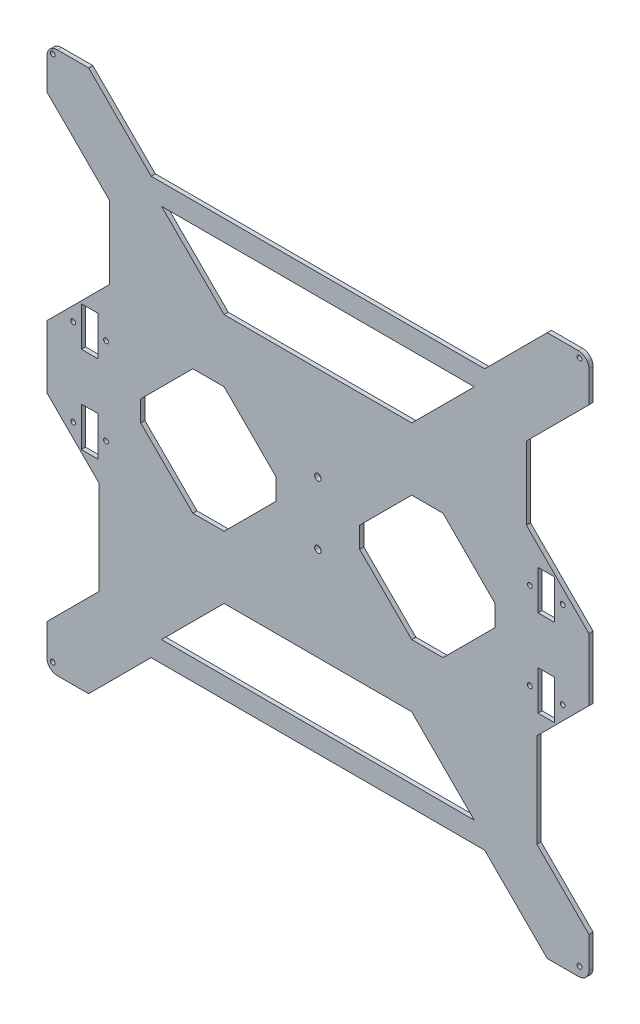
SolidWorks part; units mm, degrees
ref_plane "Front Plane" through (0, 0, 0) normal (0, 0, 1) x (1, 0, 0)
ref_plane "Top Plane" through (0, 0, 0) normal (0, 1, 0) x (1, 0, 0)
ref_plane "Right Plane" through (0, 0, 0) normal (1, 0, 0) x (0, 0, -1)
sketch "Model" plane through (0, 0, 0) normal (0, 0, 1) x (1, 0, 0)
  line L0 (38.5361, 132.6139) -> (38.5361, 132.4727)
  line L1 (38.5361, -178.6774) -> (38.5361, -178.7219)
  line L2 (-253.5639, -197.5861) -> (-253.5639, -197.7273)
  line L3 (-252.5813, 70.3317) -> (-252.5813, 25.8817)
  line L4 (-258.9313, -82.0683) -> (-258.9313, -139.2183)
  line L5 (38.5361, 132.6139) -> (38.5361, 132.4727)
  line L6 (38.5361, -178.6774) -> (38.5361, -178.7219)
  line L7 (7.7687, -139.2183) -> (7.7687, -82.0683)
  line L8 (1.4187, 25.8817) -> (1.4187, 70.3317)
  line L9 (-23.9813, 95.7317) -> (-227.1813, 95.7317)
  line L10 (-290.6813, 108.4317) -> (-252.5813, 70.3317)
  line L11 (-30.3313, -145.5683) -> (-68.4313, -107.4683)
  line L12 (-23.9813, -158.2683) -> (14.1187, -196.3683)
  line L13 (39.5187, 108.4317) -> (39.5187, 127.4817)
  line L14 (-227.1813, 95.7317) -> (-265.2813, 133.8317)
  line L15 (-220.8313, 83.0317) -> (-182.7313, 44.9317)
  line L16 (-274.6813, -57.7288) -> (-254.6813, -57.7288) construction
  line L17 (39.5187, -170.9683) -> (7.7687, -139.2183)
  line L18 (-265.2813, -196.3683) -> (-227.1813, -158.2683)
  line L19 (-182.7313, -107.4683) -> (-68.4313, -107.4683)
  line L20 (-264.6813, -57.7288) -> (-264.6813, -43.5832) construction
  line L21 (1.4187, 70.3317) -> (39.5187, 108.4317)
  line L22 (-23.9813, 95.7317) -> (14.1187, 133.8317)
  line L23 (-30.3313, 83.0317) -> (-68.4313, 44.9317)
  line L25 (-258.9313, -139.2183) -> (-290.6813, -170.9683)
  line L26 (-182.7313, 44.9317) -> (-68.4313, 44.9317)
  line L27 (-220.8313, -145.5683) -> (-182.7313, -107.4683)
  line L28 (-220.8313, -145.5683) -> (-30.3313, -145.5683)
  line L29 (-258.9313, -82.0683) -> (-290.6813, -50.3183)
  line L30 (-290.6813, -12.2183) -> (-290.6813, -50.3183)
  line L31 (-274.6813, -56.2683) -> (-274.6813, -31.2683) construction
  line L32 (-290.6813, -12.2183) -> (-252.5813, 25.8817)
  line L33 (-201.7813, -69.3683) -> (-233.5313, -37.6183)
  line L34 (-182.7313, -69.3683) -> (-201.7813, -69.3683)
  line L35 (1.4187, 25.8817) -> (39.5187, -12.2183)
  line L36 (39.5187, -12.2183) -> (39.5187, -50.3183)
  line L37 (-150.9813, -37.6183) -> (-182.7313, -69.3683)
  line L38 (39.5187, -50.3183) -> (22.4579, -67.3791)
  line L39 (22.4579, -67.3791) -> (7.7687, -82.0683)
  line L40 (-100.1813, -37.6183) -> (-100.1813, -24.9183)
  line L41 (-150.9813, -37.6183) -> (-150.9813, -24.9183)
  line L42 (-150.9813, -24.9183) -> (-182.7313, 6.8317)
  line L43 (-182.7313, 6.8317) -> (-201.7813, 6.8317)
  line L44 (-201.7813, 6.8317) -> (-233.5313, -24.9183)
  line L45 (-233.5313, -24.9183) -> (-233.5313, -37.6183)
  line L46 (-17.6313, -24.9183) -> (-17.6313, -37.6183)
  line L47 (-49.3813, 6.8317) -> (-17.6313, -24.9183)
  line L48 (-220.8313, 83.0317) -> (-30.3313, 83.0317)
  line L49 (-68.4313, 6.8317) -> (-49.3813, 6.8317)
  line L50 (-100.1813, -24.9183) -> (-68.4313, 6.8317)
  line L51 (-100.1813, -37.6183) -> (-68.4313, -69.3683)
  line L52 (-68.4313, -69.3683) -> (-49.3813, -69.3683)
  line L53 (-49.3813, -69.3683) -> (-17.6313, -37.6183)
  line L58 (-265.2813, -196.3683) -> (-284.3313, -196.3683)
  line L59 (-290.6813, -190.0183) -> (-290.6813, -170.9683)
  line L60 (-290.6813, 108.4317) -> (-290.6813, 127.4817)
  line L61 (-284.3313, 133.8317) -> (-265.2813, 133.8317)
  line L62 (14.1187, 133.8317) -> (33.1687, 133.8317)
  line L64 (39.5187, -170.9683) -> (39.5187, -190.0183)
  line L65 (33.1687, -196.3683) -> (14.1187, -196.3683)
  line L71 (-227.1813, -158.2683) -> (-23.9813, -158.2683)
  line L72 (38.5361, -178.6774) -> (38.5361, -178.7219)
  line L74 (-227.1813, -158.2683) -> (-23.9813, -158.2683)
  line L75 (38.5361, -178.6774) -> (38.5361, -178.7219)
  line L77 (-125.5813, 95.7317) -> (-125.5813, -158.2683) construction
  line L78 (-290.6813, -31.2683) -> (39.5187, -31.2683) construction
  arc A0 (33.1687, -196.3683) -> (39.5187, -190.0183) centre (33.1687, -190.0183) ccw
  arc A1 (-290.6813, -190.0183) -> (-284.3313, -196.3683) centre (-284.3313, -190.0183) ccw
  arc A2 (-290.6813, 127.4817) -> (-284.3313, 133.8317) centre (-284.3313, 127.4817) cw
  arc A3 (33.1687, 133.8317) -> (39.5187, 127.4817) centre (33.1687, 127.4817) cw
  circle A4 centre (-287.1253, -190.6025) radius 1.4605
  circle A5 centre (33.7529, -190.6025) radius 1.4605
  circle A6 centre (33.7529, 130.2757) radius 1.4605
  circle A7 centre (-287.1253, 130.2757) radius 1.4605
  circle A8 centre (-274.6813, -57.7288) radius 1.4605
  circle A9 centre (-254.6813, -57.7288) radius 1.4605
  circle A10 centre (23.5187, -57.7288) radius 1.4605
  circle A11 centre (3.5187, -57.7288) radius 1.4605
  circle A12 centre (23.5187, -4.8078) radius 1.4605
  circle A13 centre (3.5187, -4.8078) radius 1.4605
  circle A14 centre (-254.6813, -4.8078) radius 1.4605
  circle A15 centre (-274.6813, -4.8078) radius 1.4605
  circle A16 centre (-125.5813, -12.2183) radius 2
  circle A17 centre (-125.5813, -50.3183) radius 2
  point P72 (-125.5813, -31.2683)
  point P79 (-290.6813, -31.2683)
  point P114 (-125.5813, 83.0317)
  point P116 (39.5187, -31.2683)
  point P120 (-233.5313, -31.2683)
  point P129 (-150.9813, -31.2683)
  point P141 (-290.6813, -180.4933)
  point P149 (-125.5813, 44.9317)
  point P156 (-17.6313, -31.2683)
  dimension "D28" = 6.35
  dimension "D29" = 6.35
  dimension "D30" = 6.35
  dimension "D31" = 6.35
  dimension "D35" = 2.921
  dimension "D36" = 2.921
  dimension "D37" = 2.921
  dimension "D38" = 2.921
  dimension "D53" = 2.921
  dimension "D54" = 2.921
  dimension "D56" = 4
  dimension "D57" = 4
  dimension "D1" = 330.2
  dimension "D2" = 330.2
  dimension "D3" = 135
  dimension "D4" = 135
  dimension "D5" = 38.1
  dimension "D6" = 135
  dimension "D7" = 135
  dimension "D8" = 19.05
  dimension "D9" = 135
  dimension "D10" = 19.05
  dimension "D11" = 31.75
  dimension "D12" = 190.5
  dimension "D13" = 114.3
  dimension "D14" = 38.1
  dimension "D15" = 114.3
  dimension "D16" = 135
  dimension "D17" = 6.35
  dimension "D18" = 38.1
  dimension "D19" = 135
  dimension "D20" = 135
  dimension "D21" = 6.35
  dimension "D22" = 19.05
  dimension "D23" = 25.4
  dimension "D24" = 38.1
  dimension "D25" = 135
  dimension "D26" = 135
  dimension "D27" = 127
  dimension "D32" = 19.05
  dimension "D33" = 19.05
  dimension "D34" = 19.05
  dimension "D39" = 38.1
  dimension "D40" = 19.05
  dimension "D41" = 38.1
  dimension "D42" = 38.1
  dimension "D43" = 135
  dimension "D44" = 19.05
  dimension "D45" = 31.75
  dimension "D46" = 135
  dimension "D47" = 320.8782
  dimension "D48" = 320.8782
  dimension "D49" = 3.556
  dimension "D50" = 3.556
  dimension "D51" = 20
  dimension "D52" = 26
  dimension "D55" = 25
  dimension "D58" = 38.1
  dimension "D59" = 19.05
extrude "Boss-Extrude1" add sketch "Model" along normal mid plane 2.54 contours A3 L62 L22 L9 L14 L61 A2 L60 L10 L3 L32 L30 L29 L4 L25 L59 A1 L58 L18 L71 L12 L65 A0 L64 L17 L7 L39 L38 L36 L35 L8 L21 L13 A17 A16 A14 A13 A12 A10 A9 region at (-125.5808, -32.1456, 0)
sketch "Sketch1" plane through (0, 0, 1.27) normal (0, 0, 1) x (1, 0, 0)
  line L1 (-269.6813, -45.7288) -> (-259.6813, -45.7288)
  line L2 (-269.6813, -45.7288) -> (-269.6813, -69.7288)
  line L3 (-269.6813, -69.7288) -> (-259.6813, -69.7288)
  line L4 (-259.6813, -45.7288) -> (-259.6813, -69.7288)
  line L5 (-269.6813, 7.1922) -> (-259.6813, 7.1922)
  line L6 (-269.6813, 7.1922) -> (-269.6813, -16.8078)
  line L7 (-269.6813, -16.8078) -> (-259.6813, -16.8078)
  line L8 (-259.6813, 7.1922) -> (-259.6813, -16.8078)
  line L9 (8.5187, 7.1922) -> (18.5187, 7.1922)
  line L10 (8.5187, 7.1922) -> (8.5187, -16.8078)
  line L11 (8.5187, -16.8078) -> (18.5187, -16.8078)
  line L12 (18.5187, 7.1922) -> (18.5187, -16.8078)
  line L13 (8.5187, -45.7288) -> (18.5187, -45.7288)
  line L14 (8.5187, -45.7288) -> (8.5187, -69.7288)
  line L15 (8.5187, -69.7288) -> (18.5187, -69.7288)
  line L16 (18.5187, -45.7288) -> (18.5187, -69.7288)
  circle A1 centre (-274.6813, -57.7288) radius 1.4605 construction
  circle A5 centre (-274.6813, -4.8078) radius 1.4605 construction
  circle A7 centre (-254.6813, -4.8078) radius 1.4605 construction
  circle A8 centre (23.5187, -4.8078) radius 1.4605 construction
  circle A9 centre (23.5187, -57.7288) radius 1.4605 construction
  dimension "D3" = 12
  dimension "D4" = 5
  dimension "D5" = 10
  dimension "D8" = 12
  dimension "D11" = 12
  dimension "D15" = 12
  dimension "D1" = 10
  dimension "D2" = 24
  dimension "D6" = 24
  dimension "D7" = 5
  dimension "D9" = 24
  dimension "D10" = 5
  dimension "D12" = 10
  dimension "D13" = 10
  dimension "D14" = 24
  dimension "D16" = 5
extrude "Cut-Extrude1" cut sketch "Sketch1" against normal blind 10
